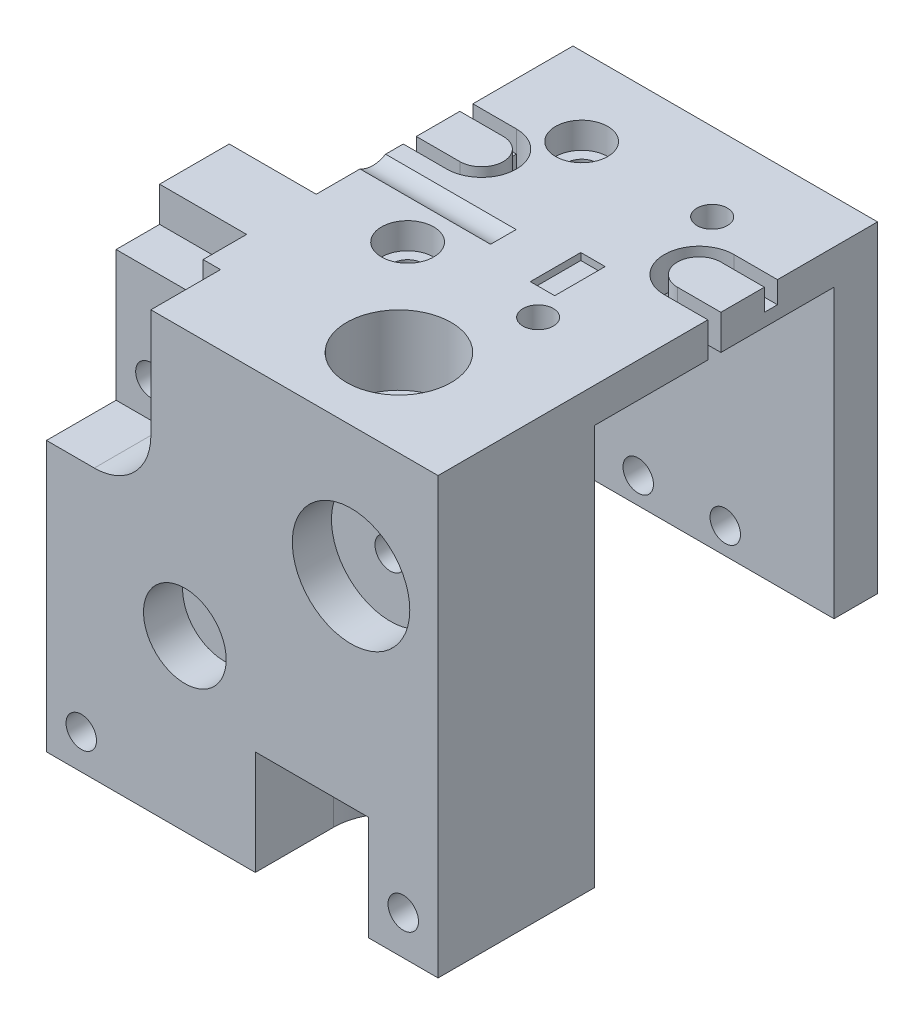
SolidWorks part; units mm, degrees
material "ABS"
ref_plane "Front Plane" through (0, 0, 0) normal (0, 0, 1) x (1, 0, 0)
ref_plane "Top Plane" through (0, 0, 0) normal (0, 1, 0) x (1, 0, 0)
ref_plane "Right Plane" through (0, 0, 0) normal (1, 0, 0) x (0, 0, -1)
sketch "Sketch1" plane through (0, 0, 0) normal (0, 1, 0) x (1, 0, 0)
  line L1 (-17.5, -14) -> (17.5, -14)
  line L2 (-17.5, -14) -> (-17.5, 14)
  line L3 (-17.5, 14) -> (17.5, 14)
  line L4 (17.5, -14) -> (17.5, 14)
  line L5 (-17.5, -14) -> (17.5, 14) construction
  line L6 (-17.5, 14) -> (17.5, -14) construction
  point P0 (0, 0)
  dimension "D1" = 28
  dimension "D2" = 35
extrude "Boss-Extrude1" add sketch "Sketch1" along normal blind 4
sketch "Sketch2" plane through (0, 4, 0) normal (0, 1, 0) x (1, 0, 0)
  line L0 (-17.5, -14) -> (17.5, -14) construction
  line L1 (-17.5, 14) -> (-17.5, -14) construction
  line L2 (-17.5, -14) -> (17.5, -14) construction
  line L3 (17.5, 14) -> (-17.5, 14) construction
  circle A0 centre (-7.5, -10) radius 1.75
  circle A1 centre (-7.5, 10) radius 1.75
  circle A2 centre (7.5, -10) radius 1.75
  circle A3 centre (7.5, 10) radius 1.75
  dimension "D1" = 3.5
  dimension "D2" = 3.5
  dimension "D5" = 3.5
  dimension "D8" = 3.5
  dimension "D3" = 20
  dimension "D4" = 4
  dimension "D6" = 15
  dimension "D7" = 10
  dimension "D9" = 15
  dimension "D10" = 4
  dimension "D11" = 4
extrude "Cut-Extrude1" cut sketch "Sketch2" against normal through all
sketch "Sketch3" plane through (0, 0, 14) normal (0, 0, 1) x (1, 0, 0)
  line L0 (17.5, 4) -> (17.5, 0) construction
  line L1 (-17.5, 4) -> (17.5, 4)
  line L2 (-17.5, 4) -> (-17.5, -46)
  line L3 (-17.5, -46) -> (17.5, -46)
  line L4 (17.5, 4) -> (17.5, -46)
  dimension "D1" = 50
extrude "Boss-Extrude2" add sketch "Sketch3" along normal blind 17.5 and the other way blind 0.5
sketch "Sketch7" plane through (0, 0, -14) normal (0, 0, -1) x (-1, 0, 0)
  line L1 (-17.5, 4) -> (17.5, 4)
  line L2 (-17.5, 4) -> (-17.5, -33)
  line L3 (-17.5, -33) -> (17.5, -33)
  line L4 (17.5, 4) -> (17.5, -33)
  line L6 (17.5, 4) -> (17.5, 0) construction
  dimension "D1" = 37
extrude "Boss-Extrude3" add sketch "Sketch7" along normal blind 5
sketch "Sketch10" plane through (0, 0, -19) normal (0, 0, -1) x (-1, 0, 0)
  line L1 (0, 4) -> (0, -33) construction
  line L3 (17.5, 4) -> (-17.5, 4) construction
  line L4 (-17.5, -33) -> (17.5, -33) construction
  circle A1 centre (-5, -30) radius 1.75
  circle A2 centre (5, -30) radius 1.75
  dimension "D1" = 3
  dimension "D2" = 3.5
  dimension "D4" = 3.5
  dimension "D3" = 5
  dimension "D5" = 5
extrude "Cut-Extrude6" cut sketch "Sketch10" against normal blind 5
sketch "Sketch18" plane through (0, 4, 0) normal (0, 1, 0) x (1, 0, 0)
  line L0 (-17.5, -10) -> (-10.5, -10)
  line L1 (-17.5, 19) -> (-17.5, -31.5) construction
  line L2 (-10.5, -10) -> (-10.5, -11.5)
  line L3 (-10.5, -11.5) -> (-17.5, -11.5)
  line L4 (-17.5, -11.5) -> (-17.5, -10)
  line L5 (17.5, 10) -> (10.5, 10)
  line L6 (17.5, -31.5) -> (17.5, 19) construction
  line L7 (10.5, 10) -> (10.5, 11.5)
  line L8 (10.5, 11.5) -> (17.5, 11.5)
  line L9 (17.5, 11.5) -> (17.5, 10)
  circle A0 centre (-7.5, -10) radius 1.75 construction
  circle A1 centre (7.5, 10) radius 1.75 construction
  dimension "D4" = 3
  dimension "D1" = 0
  dimension "D2" = 3
  dimension "D3" = 1.5
  dimension "D5" = 0
  dimension "D6" = 1.5
extrude "Cut-Extrude14" [suppressed] cut sketch "Sketch18" against normal through all
sketch "Sketch19" plane through (0, 4, 0) normal (0, 1, 0) x (1, 0, 0)
  line L0 (-17.5, 19) -> (-17.5, -31.5) construction
  line L1 (17.5, -31.5) -> (17.5, 19) construction
  circle A0 centre (-7.5, 0) radius 1.75
  circle A1 centre (7.5, 0) radius 1.75
  dimension "D3" = 3.5
  dimension "D4" = 3.5
  dimension "D1" = 10
  dimension "D2" = 10
extrude "Cut-Extrude15" [suppressed] cut sketch "Sketch19" against normal through all
sketch "Sketch20" [suppressed] plane through (0, 0, 0) normal (0, -1, 0) x (1, 0, 0)
  line L1 (10.9641, 0) -> (9.2321, 3)
  line L2 (9.2321, 3) -> (5.7679, 3)
  line L3 (5.7679, 3) -> (4.0359, 0)
  line L4 (4.0359, 0) -> (5.7679, -3)
  line L5 (5.7679, -3) -> (9.2321, -3)
  line L6 (9.2321, -3) -> (10.9641, 0)
  line L7 (-10.9641, 0) -> (-9.2321, -3)
  line L8 (-9.2321, -3) -> (-5.7679, -3)
  line L9 (-5.7679, -3) -> (-4.0359, 0)
  line L10 (-4.0359, 0) -> (-5.7679, 3)
  line L11 (-5.7679, 3) -> (-9.2321, 3)
  line L12 (-9.2321, 3) -> (-10.9641, 0)
  circle A0 centre (7.5, 0) radius 3 construction
  circle A1 centre (-7.5, 0) radius 3 construction
  dimension "D1" = 6
  dimension "D2" = 6
extrude "Cut-Extrude16" [suppressed] cut sketch "Sketch20" against normal blind 3
sketch "Sketch21" [suppressed] plane through (0, 4, 0) normal (0, 1, 0) x (1, 0, 0)
  line L0 (-10.5, -10) -> (-17.5, -10) construction
  circle A0 centre (-17, -10) radius 0.5
  dimension "D1" = 1
extrude "Cut-Extrude17" [suppressed] cut sketch "Sketch21" against normal blind 4
pattern_linear "LPattern2" [suppressed] count 4 spacing 2 of bodies 121
fillet "Fillet2" [suppressed] radius 0.15
sketch "Sketch24" plane through (-17.5, 0, 0) normal (-1, 0, 0) x (0, 0, 1)
  line L5 (31.5, -46) -> (13.5, -46) construction
  line L6 (13.5, -46) -> (31.5, -46)
  line L7 (13.5, -46) -> (13.5, 0)
  line L8 (13.5, 0) -> (31.5, 0)
  line L9 (31.5, -46) -> (31.5, 0)
  line L10 (13.5, 0) -> (13.5, -46) construction
  line L11 (31.5, 4) -> (31.5, -46) construction
extrude "Boss-Extrude4" add sketch "Sketch24" along normal blind 10
sketch "Sketch37" plane through (-17.5, 0, 0) normal (-1, 0, 0) x (0, 0, 1)
  line L0 (-19, 4) -> (31.5, 4) construction
  line L1 (10.5, 4) -> (18.5, 4)
  line L2 (10.5, 4) -> (10.5, -10)
  line L3 (10.5, -10) -> (18.5, -10)
  line L4 (18.5, 4) -> (18.5, -10)
  dimension "D1" = 3
  dimension "D2" = 5
  dimension "D3" = 14
extrude "Boss-Extrude9" add sketch "Sketch37" along normal blind 10
sketch "Sketch22" plane through (0, 0, 31.5) normal (0, 0, 1) x (1, 0, 0)
  line L0 (-27.5, -46) -> (-27.5, 0) construction
  line L1 (-15.5, 0) -> (-27.5, 0)
  line L2 (-27.5, -46) -> (17.5, -46) construction
  line L4 (-27.5, 0) -> (-17.5, 0) construction
  line L5 (-27.5, -46) -> (17.5, -46) construction
  line L6 (-27.5, 0) -> (-27.5, -15)
  line L9 (-27.5, -15) -> (-22, -15)
  line L10 (-15.5, 0) -> (-15.5, -8.5)
  line L11 (9.5, -46) -> (-3.5, -46)
  line L12 (9.5, -46) -> (9.5, -34)
  line L13 (9.5, -34) -> (-3.5, -34)
  line L14 (-3.5, -46) -> (-3.5, -34)
  line L16 (-15.5, 0) -> (-17.5, 0)
  line L17 (-15.5, 0) -> (-15.5, 4)
  line L18 (-15.5, 4) -> (-17.5, 4)
  line L19 (-17.5, 0) -> (-17.5, 4)
  circle A0 centre (-23.5, -42) radius 1.75
  circle A1 centre (13.5, -41.5) radius 1.75
  circle A3 centre (7.5, -11) radius 6.75
  circle A4 centre (-11.6, -26.5) radius 4.75
  arc A5 (-22, -15) -> (-15.5, -8.5) centre (-22, -8.5) ccw
  circle A6 centre (7.5, -11) radius 1.75
  circle A7 centre (-23.5, -11) radius 1.75
  point P21 (-15.5, -15)
  line M3 (-17.5, 4) -> (-17.5, 0)
  line M6 (17.5, 4) -> (-17.5, 4)
  line M24 (-17.5, 0) -> (-27.5, 0)
  line M25 (-27.5, 0) -> (-27.5, -46)
  dimension "D3" = 3.5
  dimension "D6" = 35
  dimension "D7" = 3.5
  dimension "D9" = 13.5
  dimension "D11" = 9.5
  dimension "D15" = 6.5
  dimension "D22" = 3.5
  dimension "D23" = 3.5
  dimension "D2" = 4
  dimension "D4" = 4.5
  dimension "D5" = 4
  dimension "D8" = 12
  dimension "D10" = 35
  dimension "D12" = 15.9
  dimension "D13" = 19.5
  dimension "D14" = 31
  dimension "D16" = 24
  dimension "D17" = 13
  dimension "D18" = 12
  dimension "D19" = 41
  dimension "D20" = 4
  dimension "D21" = 35
extrude "Cut-Extrude19" cut sketch "Sketch22" against normal up to next contours A0 | A1 | A7 | A6 region at (-23.5, -42, 31.5) region at (13.5, -41.5, 31.5) region at (7.5, -11, 31.5) region at (-23.5, -11, 31.5)
extrude "Cut-Extrude20" cut sketch "Sketch22<3>" against normal blind 4.5 contours A3 | A4
sketch "Sketch22<3>" plane through (0, 0, 31.5) normal (0, 0, 1) x (1, 0, 0) same geometry as "Sketch22"
extrude "Cut-Extrude24" cut sketch "Sketch22<5>" against normal blind 8 contours L9 A5 L10 L1 A7 M24 M25 | L1 L17 M6 M3 region at (-21.6364, -6.9513, 31.5) region at (-16.5, 2, 31.5)
sketch "Sketch22<5>" plane through (0, 0, 31.5) normal (0, 0, 1) x (1, 0, 0) same geometry as "Sketch22"
extrude "Cut-Extrude21" cut sketch "Sketch22<4>" against normal blind 15.5 contours L14 L13 L12 L11
sketch "Sketch22<4>" plane through (0, 0, 31.5) normal (0, 0, 1) x (1, 0, 0) same geometry as "Sketch22"
fillet "Fillet3" radius 6.5 2 edges at (9.5, -40, 16) (-3.5, -40, 16)
sketch "Sketch26" plane through (0, -34, 0) normal (0, -1, 0) x (1, 0, 0)
  line L0 (9.5, 31.5) -> (-3.5, 31.5) construction
  line L1 (-3.5, 22.5) -> (-3.5, 31.5) construction
  circle A0 centre (3, 21.5) radius 2.25
  dimension "D1" = 4.5
  dimension "D2" = 10
  dimension "D3" = 6.5
extrude "Cut-Extrude22" cut sketch "Sketch26" against normal through all
sketch "Sketch27" plane through (0, 4, 0) normal (0, 1, 0) x (1, 0, 0)
  circle A0 centre (3, -21.5) radius 6
  dimension "D1" = 12
extrude "Cut-Extrude23" cut sketch "Sketch27" against normal blind 8
sketch "Sketch29" plane through (0, 0, 13.5) normal (0, 0, -1) x (-1, 0, 0)
  line L1 (-4.0359, -11) -> (-5.7679, -8)
  line L2 (-5.7679, -8) -> (-9.2321, -8)
  line L3 (-9.2321, -8) -> (-10.9641, -11)
  line L4 (-10.9641, -11) -> (-9.2321, -14)
  line L5 (-9.2321, -14) -> (-5.7679, -14)
  line L6 (-5.7679, -14) -> (-4.0359, -11)
  line L7 (20.0359, -11) -> (21.7679, -14)
  line L8 (21.7679, -14) -> (25.2321, -14)
  line L9 (25.2321, -14) -> (26.9641, -11)
  line L10 (26.9641, -11) -> (25.2321, -8)
  line L11 (25.2321, -8) -> (21.7679, -8)
  line L12 (21.7679, -8) -> (20.0359, -11)
  line L13 (-10.0359, -41.5) -> (-11.7679, -38.5)
  line L14 (-11.7679, -38.5) -> (-15.2321, -38.5)
  line L15 (-15.2321, -38.5) -> (-16.9641, -41.5)
  line L16 (-16.9641, -41.5) -> (-15.2321, -44.5)
  line L17 (-15.2321, -44.5) -> (-11.7679, -44.5)
  line L18 (-11.7679, -44.5) -> (-10.0359, -41.5)
  line L19 (20.0359, -42) -> (21.7679, -45)
  line L20 (21.7679, -45) -> (25.2321, -45)
  line L21 (25.2321, -45) -> (26.9641, -42)
  line L22 (26.9641, -42) -> (25.2321, -39)
  line L23 (25.2321, -39) -> (21.7679, -39)
  line L24 (21.7679, -39) -> (20.0359, -42)
  circle A0 centre (-7.5, -11) radius 3 construction
  circle A1 centre (23.5, -11) radius 3 construction
  circle A2 centre (-13.5, -41.5) radius 3 construction
  circle A3 centre (23.5, -42) radius 3 construction
  dimension "D1" = 6
  dimension "D2" = 6
  dimension "D3" = 6
  dimension "D4" = 6
extrude "Cut-Extrude25" cut sketch "Sketch29" against normal blind 2 and the other way blind 3
sketch "Sketch30" plane through (0, 4, 0) normal (0, 1, 0) x (1, 0, 0)
  circle A0 centre (-7.5, 10) radius 3
  circle A1 centre (-7.5, -10) radius 3
  dimension "D1" = 6
  dimension "D2" = 6
extrude "Cut-Extrude26" cut sketch "Sketch30" against normal blind 3
sketch "Sketch31" plane through (0, 4, 0) normal (0, 1, 0) x (1, 0, 0)
  line L0 (-17.5, 0) -> (17.5, 0) construction
  line L1 (-17.5, 19) -> (-17.5, -10.5) construction
  line L2 (17.5, -31.5) -> (17.5, 19) construction
  line L4 (-17.5, 1) -> (-12.5, 1)
  line L10 (-17.5, -0.5) -> (-12.5, -0.5)
  line L11 (-17.5, 1) -> (-17.5, -0.5)
  line L12 (-12.5, 6) -> (-12.5, 7.5)
  arc A0 (-12.5, 1) -> (-12.5, 6) centre (-12.5, 3.5) ccw
  arc A2 (-12.5, -0.5) -> (-12.5, 7.5) centre (-12.5, 3.5) ccw
  dimension "D4" = 2.5
  dimension "D1" = 1
  dimension "D2" = 1.5
  dimension "D3" = 5
extrude "Cut-Extrude27" cut sketch "Sketch31" against normal through all
sketch "Sketch32" plane through (0, 4, 0) normal (0, 1, 0) x (1, 0, 0)
  line L0 (-17.5, 19) -> (-17.5, 1) construction
  line L1 (-12.5, 7.5) -> (-17.5, 7.5)
  line L2 (-12.5, 7.5) -> (-12.5, 6)
  line L3 (-12.5, 6) -> (-17.5, 6)
  line L4 (-17.5, 7.5) -> (-17.5, 6)
  arc A0 (-12.5, -0.5) -> (-12.5, 7.5) centre (-12.5, 3.5) ccw construction
extrude "Cut-Extrude28" cut sketch "Sketch32" against normal blind 2.5
sketch "Sketch33" plane through (-17.5, 0, 0) normal (-1, 0, 0) x (0, 0, 1)
  line L0 (0.5, 0) -> (0.5, 4) construction
  line L1 (0.5, 4) -> (10.5, 4) construction
  circle A0 centre (4, 6.5) radius 2.9
  dimension "D3" = 5.8
  dimension "D1" = 3.5
  dimension "D2" = 2.5
extrude "Cut-Extrude29" cut sketch "Sketch33" against normal blind 15
sketch "Sketch34" plane through (0, 4, 0) normal (0, 1, 0) x (1, 0, 0)
  line L1 (3.5, -6.9) -> (6.3, -6.9)
  line L2 (3.5, -6.9) -> (3.5, -1.1)
  line L3 (3.5, -1.1) -> (6.3, -1.1)
  line L4 (6.3, -6.9) -> (6.3, -1.1)
  circle A0 centre (7.5, -10) radius 1.75 construction
  dimension "D1" = 2.8
  dimension "D2" = 5.8
  dimension "D3" = 3.1
  dimension "D4" = 1.2
extrude "Cut-Extrude30" cut sketch "Sketch34" against normal blind 0.8
ref_plane "Plane1" through (0, 0, 0) normal (-1, 0, 0) x (0, 0, 1)
mirror "Mirror1" about plane through (0, 0, 0) normal (-1, 0, 0) of "Cut-Extrude28", "Cut-Extrude27"
